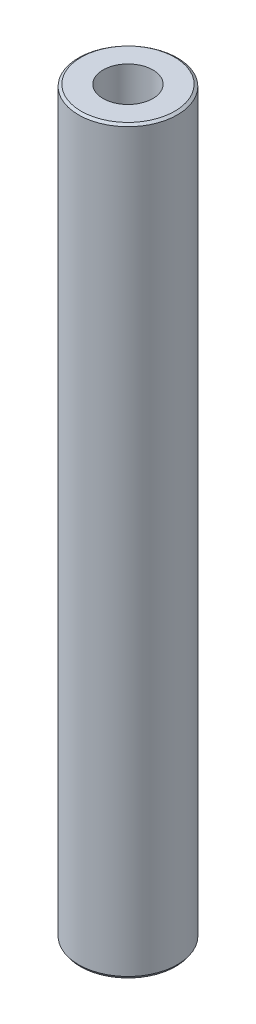
SolidWorks part; units mm, degrees
ref_plane "Front Plane" through (0, 0, 0) normal (0, 0, 1) x (1, 0, 0)
ref_plane "Top Plane" through (0, 0, 0) normal (0, 1, 0) x (1, 0, 0)
ref_plane "Right Plane" through (0, 0, 0) normal (1, 0, 0) x (0, 0, -1)
sketch "Sketch1" plane through (0, 0, 0) normal (0, 1, 0) x (1, 0, 0)
  circle A0 centre (0, 0) radius 32.5
  dimension "SHAFT_OD" = 65
extrude "Boss-Extrude1" add sketch "Sketch1" along normal blind 486.8961
sketch "Sketch2" plane through (0, 0, 0) normal (0, 1, 0) x (1, 0, 0)
  circle A0 centre (0, 0) radius 16.355
  dimension "BORE_D" = 32.71
extrude "Cut-Extrude1" cut sketch "Sketch2" along normal through all
chamfer "Chamfer1" distance 1.2138 angle 54.912 2 edges at (0, 486.8961, 32.5) (0, 0, 32.5) first distance on face at (0, 486.8961, 32.5) first distance on face at (0, 0, 16.355)
